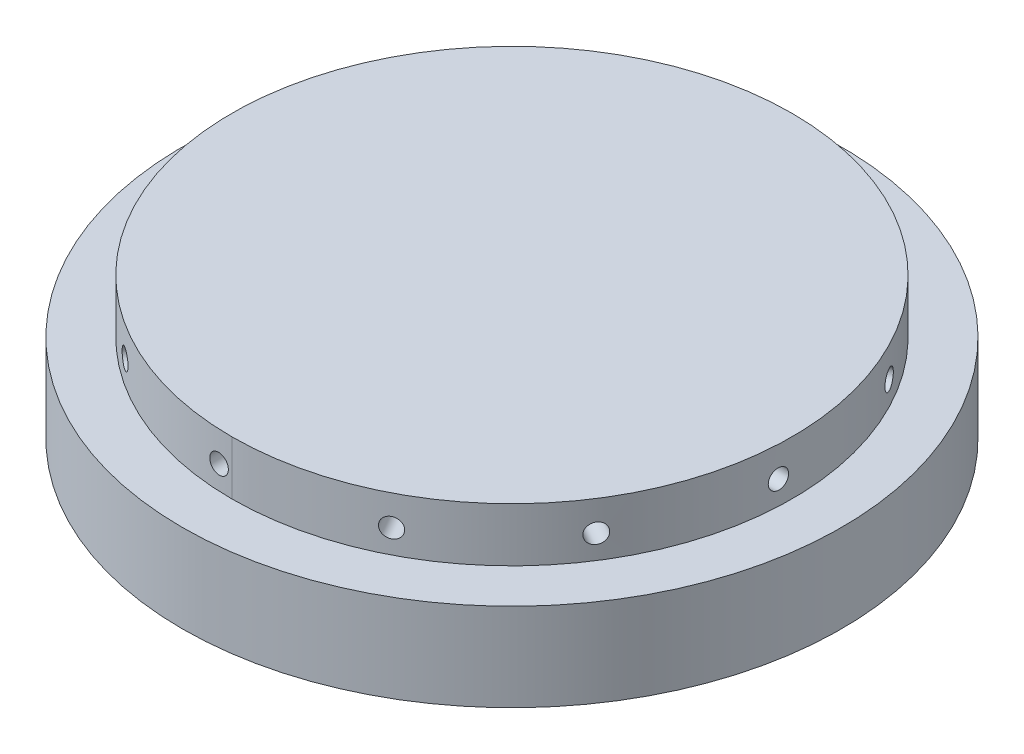
SolidWorks part; units mm, degrees
ref_plane "Front Plane" through (0, 0, 0) normal (0, 0, 1) x (1, 0, 0)
ref_plane "Top Plane" through (0, 0, 0) normal (0, 1, 0) x (1, 0, 0)
ref_plane "Right Plane" through (0, 0, 0) normal (1, 0, 0) x (0, 0, -1)
sketch "Sketch1" plane through (0, 0, 0) normal (0, 1, 0) x (1, 0, 0)
  circle A0 centre (0, 0) radius 64.77
  circle A1 centre (0, 0) radius 76.2
  circle A2 centre (0, 0) radius 56.1975
  circle A4 centre (0, 0) radius 62.865
  dimension "D1" = 152.4
  dimension "D3" = 112.395
  dimension "D2" = 129.54
  dimension "D4" = 13.335
extrude "Boss-Extrude1" add sketch "Sketch1" along normal blind 17.526 contours A0 A2 | A0 A4 region at (-62.938, 0, 0) region at (-61.0869, 0, 0)
extrude "Boss-Extrude2" add sketch "Sketch1<4>" along normal blind 5.08 and the other way blind 15.24 contours A1 A0 | A0 A4 region at (-62.938, 0, 0) region at (-74.0447, 0, 0)
sketch "Sketch1<4>" plane through (0, 0, 0) normal (0, 1, 0) x (1, 0, 0) same geometry as "Sketch1"
sketch "Sketch3" plane through (0, -15.24, 0) normal (0, -1, 0) x (1, 0, 0)
  line L0 (0, 0) -> (-65.7887, 5.7558) construction
  line L1 (0, 0) -> (0, 69.85) construction
  line L2 (0, 0) -> (48.9804, 58.3726)
  line L3 (0, 0) -> (13.232, 75.0424)
  line L4 (-13.335, -54.5925) -> (-13.335, -60.117)
  line L5 (13.335, -54.5925) -> (13.335, -60.117)
  line L6 (-13.335, -60.117) -> (13.335, -60.117)
  line L7 (-13.335, -60.117) -> (-13.335, -61.4344)
  line L8 (-23.7501, -50.9322) -> (-26.5679, -56.975)
  line L9 (0, 0) -> (-23.7501, -50.9322) construction
  line L10 (-65.2934, 11.4174) -> (-61.874, 11.1182)
  line L11 (-66.284, 0.0941) -> (-62.8647, -0.205)
  line L12 (-66.0236, -5.8708) -> (-62.6433, -5.2748)
  line L13 (-64.0498, -17.0646) -> (-60.6695, -16.4686)
  line L14 (-65.0367, -11.4677) -> (0, 0) construction
  line L15 (27.9275, 60.1135) -> (26.7536, 56.8881)
  line L16 (17.2465, 64.0011) -> (16.0725, 60.7757)
  line L17 (38.0961, -54.2427) -> (35.8898, -51.6133)
  line L18 (46.8033, -46.9365) -> (44.597, -44.3071)
  line L19 (-3.0468, 69.7835) -> (0, 0) construction
  line L20 (0, 0) -> (-21.0043, 66.6171) construction
  circle A0 centre (-65.7887, 5.7558) radius 5.6833
  circle A1 centre (-3.0468, 69.7835) radius 1.3589
  circle A2 centre (0, 0) radius 76.2 construction
  circle A5 centre (0, 0) radius 56.1975 construction
  arc A7 (-26.5679, -56.975) -> (-13.335, -61.4344) centre (0, 0) ccw
  arc A9 (-23.7501, -50.9322) -> (-13.335, -54.5925) centre (0, 0) ccw
  circle A10 centre (-65.7887, 5.7558) radius 2.5083
  circle A11 centre (-65.0367, -11.4677) radius 5.6832
  circle A13 centre (-65.0367, -11.4677) radius 2.5082
  circle A14 centre (0, 0) radius 62.865 construction
  circle A15 centre (22.587, 62.0573) radius 5.6832
  circle A16 centre (22.587, 62.0573) radius 2.5082
  circle A17 centre (42.4497, -50.5896) radius 5.6832
  circle A18 centre (42.4497, -50.5896) radius 2.5082
  arc A19 (-62.6433, -5.2748) -> (-60.6695, -16.4686) centre (0, 0) ccw
  circle A20 centre (-21.0043, 66.6171) radius 1.5
  circle A21 centre (0, 0) radius 62.865
  point P0 (0, -60.117)
  point P38 (0, 0)
  point P56 (0, 0)
  circle M49 centre (0, 0) radius 62.865
  dimension "D4" = 11.3665
  dimension "D5" = 2.7178
  dimension "D11" = 5.0165
  dimension "D17" = 3
  dimension "D1" = 66.04
  dimension "D3" = 69.85
  dimension "D6" = 30
  dimension "D7" = 10
  dimension "D9" = 26.67
  dimension "D8" = 5.5245
  dimension "D10" = 25
  dimension "D2" = 82.5
  dimension "D15" = 2.5
  dimension "D16" = 15
  dimension "D12" = 15
  dimension "D14" = 3
extrude "Cut-Extrude1" cut sketch "Sketch3" against normal blind 1.8415 contours A11 A13 M49 | A11 L13 M49 | A13 | A11 L12 M49 | A0 A10 M49 | A10 | A0 L11 M49 | A0 L10 M49 region at (-62.774, -15.24, 10.8743) region at (-63.6243, -15.24, 10.8507) region at (-63.7086, -15.24, 0.1915) region at (-63.4495, -15.24, -5.7433) region at (-64.265, -15.24, -5.9885) region at (-61.5874, -15.24, -16.304) region at (-65.7887, -15.24, 5.7558) region at (-65.0367, -15.24, -11.4677)
extrude "Cut-Extrude2" cut sketch "Sketch3<3>" against normal blind 12.7 contours A1 region at (-3.0468, -15.24, 69.7835)
sketch "Sketch3<3>" plane through (0, -15.24, 0) normal (0, -1, 0) x (1, 0, 0) same geometry as "Sketch3"
sketch "Sketch6" plane through (0, -13.3985, 0) normal (0, -1, 0) x (1, 0, 0)
  line L0 (-65.0367, -11.4677) -> (0, 0) construction
  line L1 (0, 0) -> (-65.7887, 5.7558) construction
  arc A0 (-65.2934, 11.4174) -> (-66.284, 0.0941) centre (-65.7887, 5.7558) ccw construction
  arc A1 (-65.2934, 11.4174) -> (-66.284, 0.0941) centre (-65.7887, 5.7558) ccw
  circle A2 centre (-65.7887, 5.7558) radius 2.5083
  circle A3 centre (-65.0367, -11.4677) radius 2.5082
  point P9 (0, 0)
  dimension "D1" = 5.0165
  dimension "D3" = 15
  dimension "D2" = 2
extrude "Cut-Extrude4" cut sketch "Sketch6" against normal blind 12.5095 contours A3 | A2 region at (-65.0367, -13.3985, -11.4677)
pattern_circular "CirPattern2" count 12 over 360 about axis through (0, -15.24, 0) along (0, 1, 0) of "Cut-Extrude2"
ref_plane "Plane1" through (0, 0, 76.2) normal (0, 0, 1) x (1, 0, 0)
sketch "Sketch5" plane through (0, 0, 76.2) normal (0, 0, 1) x (1, 0, 0)
  line L0 (-3.0468, -15.24) -> (-3.0468, 10.5664) construction
  line L1 (-4.4057, -15.24) -> (-1.6879, -15.24) construction
  line L3 (-76.2, -15.24) -> (76.2, -15.24) construction
  line L4 (76.2, 5.08) -> (-76.2, 5.08) construction
  line L5 (-76.2, -15.24) -> (76.2, -15.24)
  line L6 (76.2, 5.08) -> (-76.2, 5.08)
  circle A0 centre (-3.0468, 10.5664) radius 2.2479
  dimension "D2" = 4.4958
  dimension "D1" = 5.4864
extrude "Cut-Extrude3" cut sketch "Sketch5" against normal up to surface (20.0082 mm away) contours A0 region at (-3.0468, 10.5664, 76.2) up to face at (0, 17.526, 56.1975)
extrude "Boss-Extrude3" add sketch "Sketch3<11>" along normal blind 10.16 from surface contours L4 A9 L8 A7 L7 starting at face at (0, 0, 56.1975)
sketch "Sketch3<11>" plane through (0, -15.24, 0) normal (0, -1, 0) x (1, 0, 0) same geometry as "Sketch3"
pattern_circular "CirPattern3" count 6 over 360 about axis through (0, 17.526, 0) along (0, 1, 0) of "Boss-Extrude3"
fillet "Fillet1" radius 1.5875 12 edges at (-62.6258, -5.08, -5.479) (-59.8713, -5.08, -19.1688) (-26.5679, -5.08, -56.975) (-13.335, -5.08, -61.4344) (36.0579, -5.08, -51.496) (46.5363, -5.08, -42.2657) (62.6258, -5.08, 5.479) (59.8713, -5.08, 19.1688) (26.5679, -5.08, 56.975) (13.335, -5.08, 61.4344) (-36.0579, -5.08, 51.496) (-46.5363, -5.08, 42.2657)
pattern_circular "CirPattern4" count 12 over 360 about axis through (0, 17.526, 0) along (0, 1, 0) of "Cut-Extrude3"
sketch "Sketch8" plane through (0, 17.526, 0) normal (0, 1, 0) x (1, 0, 0)
  arc A0 (-34.7117, -52.4129) -> (12.0518, -61.699) centre (0, 0) ccw construction
  arc A1 (-34.7117, -52.4129) -> (12.0518, -61.699) centre (0, 0) ccw
  circle A2 centre (0, 0) radius 62.865
  circle M2 centre (0, 0) radius 56.1975
extrude "Cut-Extrude5" [suppressed] cut sketch "Sketch8" against normal up to surface (17.526 mm away) contours A1 A2 M2 up to face at (42.8898, 0, 37.3465)
sketch "Sketch9" plane through (0, 0, 0) normal (0, 0, 1) x (1, 0, 0)
  line L0 (0, 5.08) -> (0, 17.526)
  line L1 (76.2, 5.08) -> (-76.2, 5.08) construction
  line L2 (64.77, 17.526) -> (-64.77, 17.526) construction
split line "Split Line2"
extrude "Cut-Extrude7" cut sketch "Sketch3<24>" against normal blind 7.9375 contours A20
sketch "Sketch3<24>" plane through (0, -15.24, 0) normal (0, -1, 0) x (1, 0, 0) same geometry as "Sketch3"
pattern_circular "CirPattern1" count 3 over 360 about axis through (0, -15.24, 0) along (0, 1, 0) of "Cut-Extrude1", "Cut-Extrude4", "Cut-Extrude7"
extrude "Boss-Extrude4" add sketch "Sketch1<8>" along normal up to surface (17.526 mm away) contours A2 region at (0, 0, 0) up to face at (0, 17.526, 56.1975)
sketch "Sketch1<8>" plane through (0, 0, 0) normal (0, 1, 0) x (1, 0, 0) same geometry as "Sketch1"
equation "\"Middle Coupler Inner Daimeter\"= 3.875in"
equation "\"Middle Coupler  Wall Thickness\" = 0.25in"
equation "\"Middle Coupler Bottom Thickness\"= 0.2in"
equation "\"Bearing Rail Offset\"= 0.45in"
equation "\"3-56 UNF Tap\"= 0.089in"
equation "\"3-48 Tap\"= 0.079in"
equation "\"3-56 UNF Clearance\"= 0.104in"
equation "\"3-48 Clearance\" = 0.104in"
equation "\"Ball Bearing Distance\"= 0.03in"
equation "\"TCA Outer Diameter\" = 6in"
equation "\"Interstage Aeroframe Wall Thickness\" = 0.072in"
equation "\"Compression Spring OD\"= 0.42in"
equation "\"10-24 Tap\"= 0.157in"
equation "\"10-24 Clearance\"= 0.196in"
equation "\"Lower Stage Fuselage Wall Thickness\" = 0.25in"
equation "\"6-32 Tap\" = 0.107in"
equation "\"6-32 Clearance\" = 0.144"
equation "\"1/4-20 Tap\" = 0.201in"
equation "\"12-24 Tap\" = 0.177in"
equation "\"D1@Sketch1\"=\"TCA Outer Diameter\""
equation "\"D5@Sketch3\"=\"6-32 Tap\""
equation "\"D2@Sketch5\"=\"12-24 Tap\""
equation "\"D8@Sketch3\"=3/16+0.03"
equation "\"D3@Sketch1\"=\"Middle Coupler Inner Daimeter\" + 0.55"
equation "\"D1@Boss-Extrude1\"=0.15 + \"12-24 Major Diameter\"*2.5"
equation "\"12-24 Major Diameter\"= 0.216in"
equation "\"D1@Cut-Extrude1\"=1/16 + 0.01"
equation "\"D11@Sketch3\"=3/16 + 0.01"
equation "\"D1@Sketch6\"=3/16 + 0.01"
equation "\"D1@Sketch5\"=\"12-24 Major Diameter\""
equation "\"D1@Cut-Extrude4\"=0.4425+0.05"
